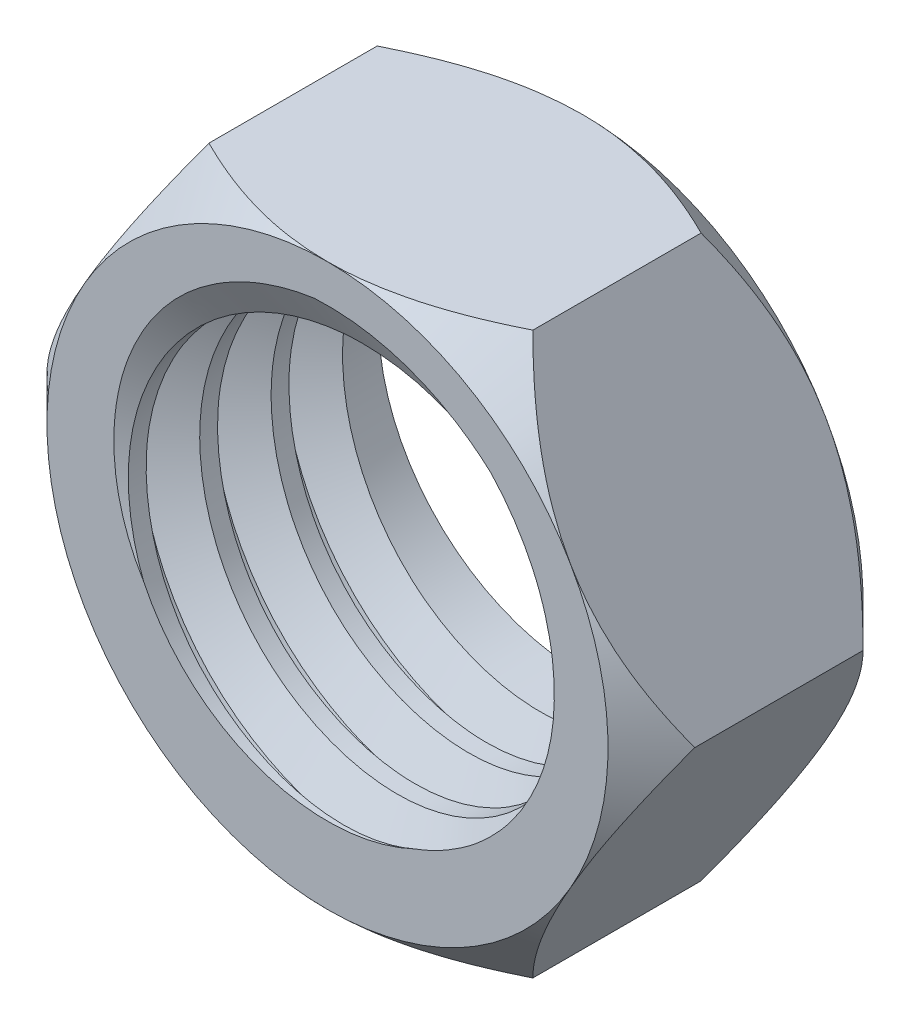
SolidWorks part; units mm, degrees
ref_plane "Front Plane" through (0, 0, 0) normal (0, 0, 1) x (1, 0, 0)
ref_plane "Top Plane" through (0, 0, 0) normal (0, 1, 0) x (1, 0, 0)
ref_plane "Right Plane" through (0, 0, 0) normal (1, 0, 0) x (0, 0, -1)
sketch "Sketch1" plane through (0, 0, 0) normal (0, 0, 1) x (1, 0, 0)
  line L0 (-3.1754, 0) -> (3.1754, 0) construction
  line L1 (3.1754, 0) -> (1.5877, 2.75)
  line L2 (1.5877, 2.75) -> (-1.5877, 2.75)
  line L3 (-1.5877, 2.75) -> (-3.1754, 0)
  line L4 (-3.1754, 0) -> (-1.5877, -2.75)
  line L5 (-1.5877, -2.75) -> (1.5877, -2.75)
  line L6 (1.5877, -2.75) -> (3.1754, 0)
  line L7 (0, -2.75) -> (0, 2.75) construction
  circle A0 centre (0, 0) radius 2.75
  circle A1 centre (0, 0) radius 2
  dimension "D1" = 5.5
  dimension "D2" = 4
extrude "Boss-Extrude1" add sketch "Sketch1" along normal blind 2.5 contours L3 L4 L5 L6 L1 L2
extrude "Cut-Extrude1" cut sketch "Sketch1<3>" along normal up to next contours A1
sketch "Sketch1<3>" plane through (0, 0, 0) normal (0, 0, 1) x (1, 0, 0) same geometry as "Sketch1"
extrude "Cut-Extrude2" cut sketch "Sketch1<4>" along normal blind 1 draft 45 flip side to cut contours A0
sketch "Sketch1<4>" plane through (0, 0, 0) normal (0, 0, 1) x (1, 0, 0) same geometry as "Sketch1"
ref_plane "Plane1" through (0, 0, 2.5) normal (0, 0, 1) x (1, 0, 0)
sketch "Sketch2" plane through (0, 0, 2.5) normal (0, 0, 1) x (1, 0, 0)
  circle A0 centre (0, 0) radius 2.75
  dimension "D1" = 5.5
extrude "Cut-Extrude3" cut sketch "Sketch2" against normal blind 1 draft 45 flip side to cut
thread "Thread1" pitch 0.7 method cut profile "Thread Profile1" start angle 0, offset 0, length 0, pitch 0.7, diameter 4
ref_plane "Plane2" through (2, 0, 0) normal (0, -1, 0) x (1, 0, 0)
sketch "Thread Profile1" plane through (2, 0, 0) normal (0, -1, 0) x (1, 0, 0)
  line L0 (0, 0) -> (0, 0.7) construction
  line L1 (0, 0) -> (0.3789, 0.2187)
  line L2 (0.3789, 0.2187) -> (0.3789, 0.3062)
  line L3 (0.3789, 0.3062) -> (0, 0.525)
  line L4 (0.3789, 0.2625) -> (0, 0.2625) construction
  line L11 (0, 0) -> (0, 0.525)
  point P2 (0, 0)
  dimension "Pitch" = 0.7
  dimension "Profile_Angle" = 60
  dimension "Profile_Land" = 0.0875
  dimension "Profile_Height" = 0.3789
